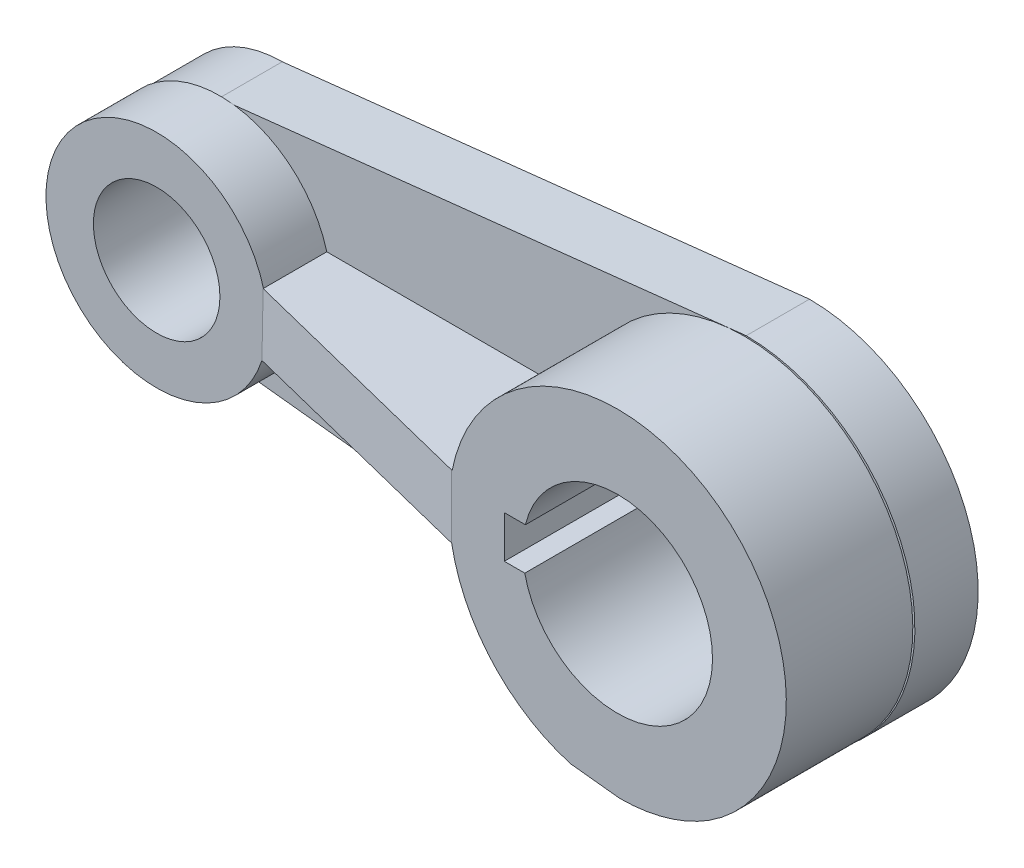
SolidWorks part; units mm, degrees
ref_plane "Front Plane" through (0, 0, 0) normal (0, 0, 1) x (1, 0, 0)
ref_plane "Top Plane" through (0, 0, 0) normal (0, 1, 0) x (1, 0, 0)
ref_plane "Right Plane" through (0, 0, 0) normal (1, 0, 0) x (0, 0, -1)
sketch "Sketch4" plane through (0, 0, 0) normal (0, 0, 1) x (1, 0, 0)
  line L0 (-47.0944, 0) -> (52.9056, 0) construction
  line L1 (-47.0944, 21) -> (52.9056, 32)
  line L2 (-47.0944, -21) -> (52.9056, -32)
  circle A0 centre (52.9056, 0) radius 32
  circle A1 centre (-47.0944, 0) radius 21
  dimension "D2" = 64
  dimension "D3" = 42
  dimension "D1" = 100
extrude "Boss-Extrude1" add sketch "Sketch4" against normal blind 12 contours A1 | L0 A1 L2 A0 | A1 L0 A0 L1 | L1 A0 L2 region at (-0.9939, 14.4208, 0) region at (-32.6652, -14.4292, 0) region at (-0.9939, -14.4208, 0) region at (52.9075, 0, 0)
sketch "Sketch7" plane through (0, 0, 0) normal (0, 0, 1) x (1, 0, 0)
  circle A0 centre (52.514, -0.2492) radius 32
  circle A1 centre (-46.9169, 0.4984) radius 21
  line M3 (-47.0944, -21) -> (52.9056, -32)
  arc M4 (52.9056, -32) -> (52.9056, 32) centre (52.9056, 0) ccw
  dimension "D1" = 42
  dimension "D2" = 64
extrude "Boss-Extrude3" add sketch "Sketch7" along normal blind 12 contours A1
extrude "Boss-Extrude4" add sketch "Sketch7<4>" along normal blind 24 contours A0 M4 M3 region at (52.5134, -0.1944, 0)
sketch "Sketch7<4>" plane through (0, 0, 0) normal (0, 0, 1) x (1, 0, 0) same geometry as "Sketch7"
sketch "Sketch9" plane through (0, 0, 0) normal (0, 0, 1) x (1, 0, 0)
  circle A0 centre (-46.9169, 0.4984) radius 12
  circle A1 centre (52.514, -0.2492) radius 18
  dimension "D1" = 24
  dimension "D2" = 36
extrude "Cut-Extrude1" cut sketch "Sketch9" against normal through all contours A1 | A0
extrude "Cut-Extrude2" cut sketch "Sketch9<3>" against normal through all both and the other way through all
sketch "Sketch9<3>" plane through (0, 0, 0) normal (0, 0, 1) x (1, 0, 0) same geometry as "Sketch9"
sketch "Sketch10" plane through (0, 0, 24) normal (0, 0, 1) x (1, 0, 0)
  line L0 (-78.3161, 0) -> (88.3988, 0) construction
  line L1 (35.0227, 4) -> (31.0227, 4)
  line L2 (31.0227, 4) -> (31.0227, -4)
  line L3 (31.0227, -4) -> (34.9091, -4)
  line L4 (35.0227, 4) -> (34.9091, -4)
  circle A0 centre (52.514, -0.2492) radius 18 construction
  dimension "D1" = 4
  dimension "D2" = 8
extrude "Cut-Extrude3" cut sketch "Sketch10" against normal through all both and the other way through all
sketch "Sketch11" plane through (0, 0, 0) normal (0, 0, 1) x (1, 0, 0)
  line L0 (-77.0701, 0) -> (91.8876, 0) construction
  line L1 (-26.6503, 6) -> (21.1301, 6)
  line L2 (-26.9476, -6) -> (21.035, -6)
  line L3 (-26.6503, 6) -> (-26.9476, -6)
  line L4 (21.1301, 6) -> (21.035, -6)
  circle A0 centre (-46.9169, 0.4984) radius 21 construction
  arc A1 (69.8902, -27.1205) -> (43.5657, -30.9726) centre (52.514, -0.2492) ccw construction
  dimension "D1" = 12
extrude "Boss-Extrude5" add sketch "Sketch11" along normal blind 24 contours L4 L2 L3 L1
sketch "Sketch12" plane through (0, -6, 0) normal (0, -1, 0) x (1, 0, 0)
  line L0 (21.035, 24) -> (-26.9476, 12)
  line L1 (-26.9476, 12) -> (-26.9476, 24)
  line M5 (21.035, 24) -> (-26.9476, 24)
  line M6 (-26.9476, 24) -> (-26.9476, 12)
extrude "Cut-Extrude4" cut sketch "Sketch12" against normal blind 24 and the other way through all contours L0 M5 M6 region at (-10.9534, -6, 20)
